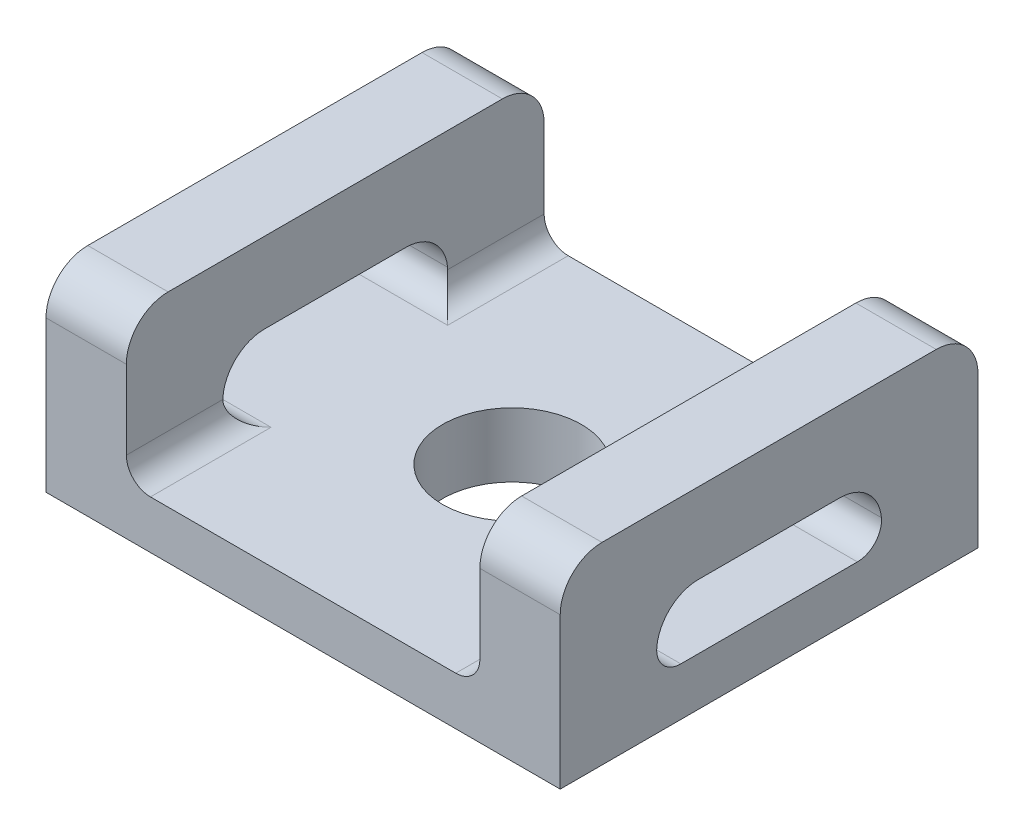
SolidWorks part; units mm, degrees
ref_plane "Front Plane" through (0, 0, 0) normal (0, 0, 1) x (1, 0, 0)
ref_plane "Top Plane" through (0, 0, 0) normal (0, 1, 0) x (1, 0, 0)
ref_plane "Right Plane" through (0, 0, 0) normal (1, 0, 0) x (0, 0, -1)
sketch "Sketch1" plane through (0, 0, 0) normal (0, 1, 0) x (1, 0, 0)
  line L1 (-8, -6.5) -> (8, -6.5)
  line L2 (-8, -6.5) -> (-8, 6.5)
  line L3 (-8, 6.5) -> (8, 6.5)
  line L4 (8, -6.5) -> (8, 6.5)
  line L5 (-8, -6.5) -> (8, 6.5) construction
  line L6 (-8, 6.5) -> (8, -6.5) construction
  circle A0 centre (0, 0) radius 2.159
  point P0 (0, 0)
  dimension "D3" = 4.318
  dimension "D1" = 16
  dimension "D2" = 13
extrude "Boss-Extrude1" add sketch "Sketch1" along normal blind 2
sketch "Sketch2" plane through (8, 0, 0) normal (1, 0, 0) x (0, 0, -1)
  line L1 (-6.5, 2) -> (6.5, 2)
  line L2 (-6.5, 2) -> (-6.5, 5.2)
  line L3 (-5.2, 6.5) -> (5.2, 6.5)
  line L4 (6.5, 2) -> (6.5, 5.2)
  line L5 (-3.5, 2) -> (3.5, 2)
  line L6 (-3.5, 2) -> (-3.5, 2.7)
  line L7 (-2.2, 4) -> (2.2, 4)
  line L8 (3.5, 2) -> (3.5, 2.7)
  arc A0 (3.5, 2.7) -> (2.2, 4) centre (2.2, 2.7) ccw
  arc A1 (-2.2, 4) -> (-3.5, 2.7) centre (-2.2, 2.7) ccw
  arc A2 (5.2, 6.5) -> (6.5, 5.2) centre (5.2, 5.2) cw
  arc A3 (-6.5, 5.2) -> (-5.2, 6.5) centre (-5.2, 5.2) cw
  point P13 (-3.5, 4)
  point P16 (6.5, 6.5)
  point P19 (-6.5, 6.5)
  line M8 (6.5, 2) -> (-6.5, 2)
  dimension "D6" = 1.3
  dimension "D7" = 1.3
  dimension "D1" = 13
  dimension "D2" = 4.5
  dimension "D3" = 3
  dimension "D4" = 3
  dimension "D5" = 2
extrude "Boss-Extrude2" add sketch "Sketch2" against normal blind 16 contours A3 L2 L6 A1 L7 A0 L8 L4 A2 L3 M8 region at (8, 4.6025, 0)
sketch "Sketch4" plane through (0, 0, 6.5) normal (0, 0, 1) x (1, 0, 0)
  line L0 (-8, 5.2) -> (-8, 0) construction
  line L1 (-5.5, 7) -> (5.5, 7)
  line L2 (-5.5, 7) -> (-5.5, 2)
  line L3 (-5.5, 2) -> (5.5, 2)
  line L4 (5.5, 7) -> (5.5, 2)
  line L5 (-8, 0) -> (8, 0) construction
  dimension "D1" = 2.5
  dimension "D2" = 2.5
  dimension "D3" = 2
  dimension "D4" = 5
extrude "Cut-Extrude1" cut sketch "Sketch4" against normal through all both and the other way through all
fillet "Fillet1" radius 0.75 8 edges at (-5.5, 2, 5) (-6.75, 2, 3.5) (6.75, 2, 3.5) (5.5, 2, 5) (5.5, 2, -5) (6.75, 2, -3.5) (-5.5, 2, -5) (-6.75, 2, -3.5)
chamfer "Chamfer1" distance 0.5 angle 45 4 edges at (0, 0, -6.5) (-8, 0, 0) (0, 0, 6.5) (8, 0, 0)
